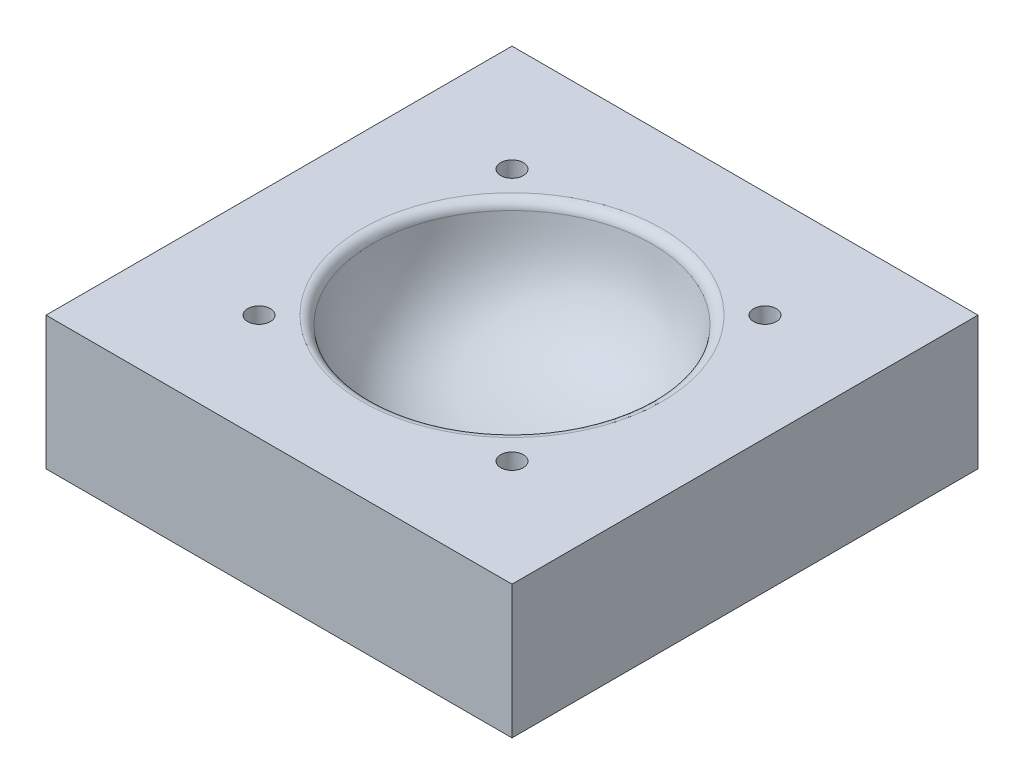
SolidWorks part; units mm, degrees
ref_plane "Front" through (0, 0, 0) normal (0, 0, 1) x (1, 0, 0)
ref_plane "Top" through (0, 0, 0) normal (0, 1, 0) x (1, 0, 0)
ref_plane "Right" through (0, 0, 0) normal (1, 0, 0) x (0, 0, -1)
sketch "Sketch2" plane through (0, 0, 0) normal (0, 1, 0) x (1, 0, 0)
  line L1 (-35, -35) -> (35, -35)
  line L2 (-35, -35) -> (-35, 35)
  line L3 (-35, 35) -> (35, 35)
  line L4 (35, -35) -> (35, 35)
  line L5 (-35, -35) -> (35, 35) construction
  line L6 (-35, 35) -> (35, -35) construction
  point P0 (0, 0)
  dimension "D1" = 70
extrude "Boss-Extrude1" add sketch "Sketch2" against normal blind 20
sketch "Sketch1" plane through (0, 0, 0) normal (0, 0, 1) x (1, 0, 0)
  line L0 (0, 0) -> (0, -14) construction
  line L1 (-15, 0) -> (15, 0) construction
  line L2 (-15, 0) -> (-15, -9) construction
  line L3 (-15, -9) -> (15, -9) construction
  line L4 (15, 0) -> (15, -9) construction
  line L5 (0, 0) -> (18, 0) construction
  line L6 (18, 0) -> (15.6756, -14.676) construction
  line L7 (-15, -20) -> (15, -20) construction
  line L8 (-15, -17) -> (15, -17) construction
  line L9 (-15, -14) -> (15, -14) construction
  line L10 (18, 0) -> (18, 4) construction
  line L11 (18, 4) -> (0, 4) construction
  line L12 (0, 4) -> (0, 0) construction
  line L13 (0, -17.2) -> (0, 0)
  line L14 (0, 0) -> (21.2417, 0)
  line L15 (-35, 0) -> (35, 0) construction
  line L16 (21.2417, 0) -> (21.1589, -0.5115)
  spline S0 degree 3 poles (0, -14) (16.3895, -14) (17.0195, -6.0548) (18, 0) knots 0 0 0 0 1 1 1 1 construction
  spline S1 degree 1 poles (0, -17.2) (21.1589, -0.5115) knots 0 0 1 1 construction
  spline S2 degree 3 poles (0, -17.2) (0.5307, -17.2) (1.6116, -17.1835) (3.6155, -17.0859) (5.9441, -16.8449) (8.4484, -16.3701) (11.4427, -15.4929) (14.5797, -13.9372) (17.3822, -11.4027) (19.199, -8.5009) (20.2357, -5.5832) (20.7065, -3.3134) (20.9819, -1.6359) (21.0969, -0.8942) (21.1589, -0.5115) knots 0 0 0 0 0.03125 0.0625 0.125 0.1875 0.25 0.375 0.5 0.625 0.75 0.875 0.9375 1 1 1 1
  dimension "D1" = 30
  dimension "D2" = 9
  dimension "D3" = 18
  dimension "D4" = 20
  dimension "D5" = 3
  dimension "D6" = 3
  dimension "D7" = 81
  dimension "D8" = 18
  dimension "D9" = 3.2
revolve "Cut-Revolve1" cut sketch "Sketch1" angle 360 about L13
fillet "Fillet1" radius 1.5 1 edges at (0, 0, -21.2417)
sketch "Sketch3" plane through (0, 0, 0) normal (0, 1, 0) x (1, 0, 0)
  line L0 (-32.7416, 0) -> (25.0655, 0) construction
  line L1 (-19, -19) -> (19, -19) construction
  line L2 (-19, -19) -> (-19, 19) construction
  line L3 (-19, 19) -> (19, 19) construction
  line L4 (19, -19) -> (19, 19) construction
  line L5 (-19, -19) -> (19, 19) construction
  line L6 (-19, 19) -> (19, -19) construction
  circle A0 centre (-19, 19) radius 1.7
  circle A1 centre (19, -19) radius 1.7
  circle A2 centre (-19, -19) radius 1.7
  circle A3 centre (19, 19) radius 1.7
  point P0 (0, 0)
  dimension "D2" = 3.4
  dimension "D1" = 38
extrude "Cut-Extrude1" cut sketch "Sketch3" against normal through all
